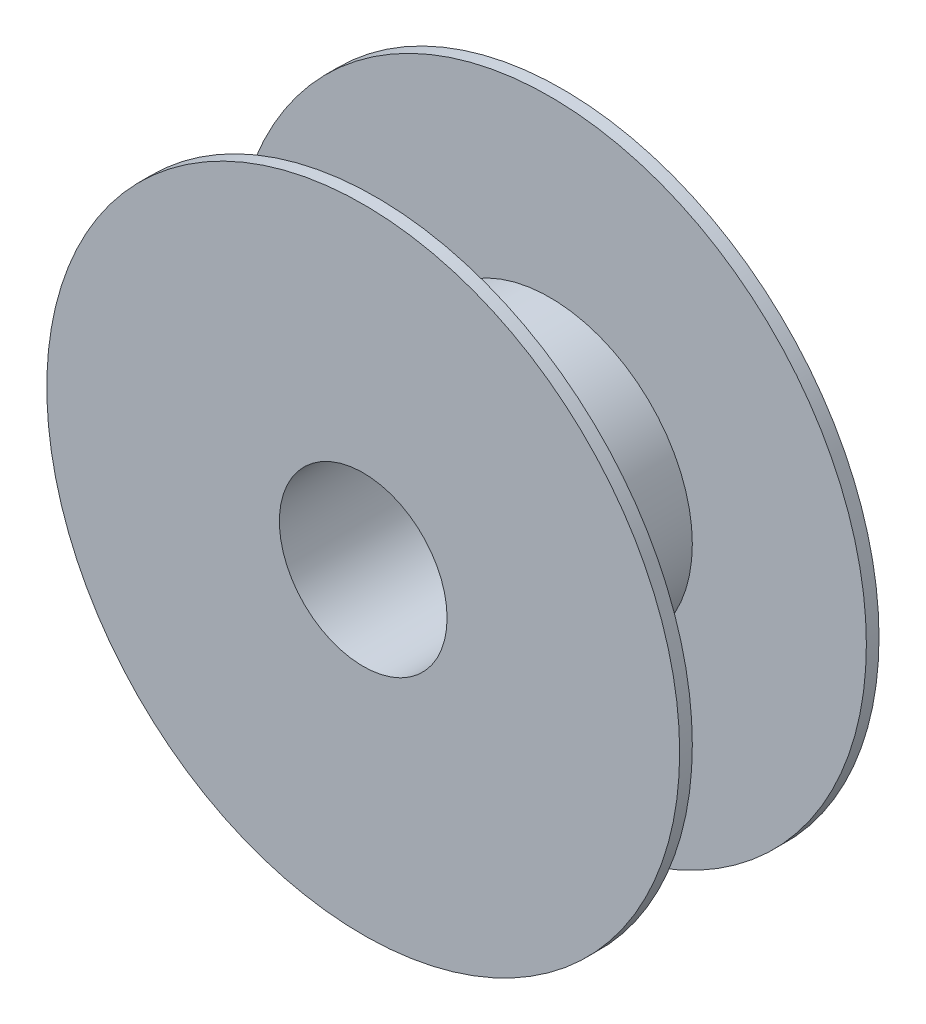
SolidWorks part; units mm, degrees
ref_plane "Front Plane" through (0, 0, 0) normal (0, 0, 1) x (1, 0, 0)
ref_plane "Top Plane" through (0, 0, 0) normal (0, 1, 0) x (1, 0, 0)
ref_plane "Right Plane" through (0, 0, 0) normal (1, 0, 0) x (0, 0, -1)
sketch "Sketch1" plane through (0, 0, 0) normal (0, 0, 1) x (1, 0, 0)
  circle A0 centre (0, 0) radius 100
  circle A1 centre (0, 0) radius 26.5
  dimension "D1" = 53
  dimension "D2" = 200
extrude "Boss-Extrude1" add sketch "Sketch1" along normal mid plane 63
sketch "Sketch2" plane through (0, 0, 0) normal (0, 0, 1) x (1, 0, 0)
  circle A0 centre (0, 0) radius 100
  circle A1 centre (0, 0) radius 45
  dimension "D1" = 200
  dimension "D2" = 90
extrude "Cut-Extrude1" cut sketch "Sketch2" against normal mid plane 55
ref_axis "Axis1" through (0, 0, -34.65) along (0, 0, 1)
